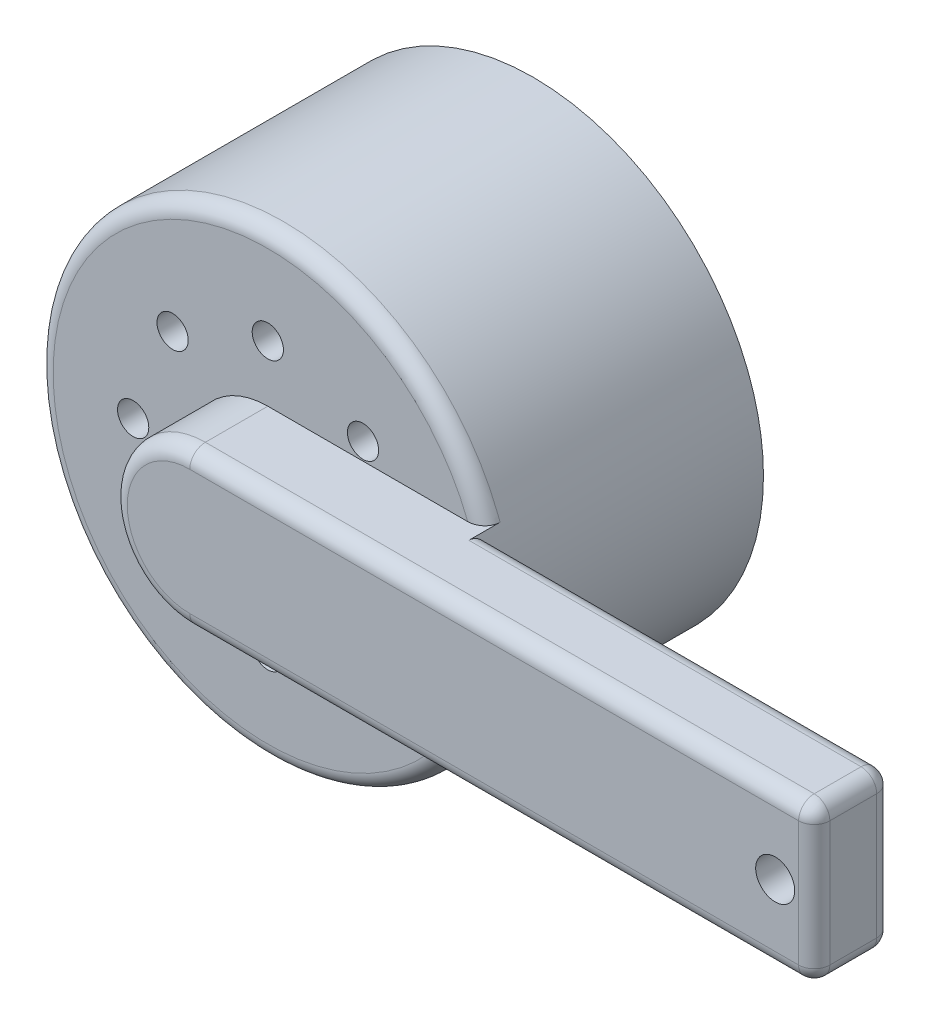
SolidWorks part; units mm, degrees
ref_plane "前视基准面" through (0, 0, 0) normal (0, 0, 1) x (1, 0, 0)
ref_plane "上视基准面" through (0, 0, 0) normal (0, 1, 0) x (1, 0, 0)
ref_plane "右视基准面" through (0, 0, 0) normal (1, 0, 0) x (0, 0, -1)
other "Configuration Table"
sketch "草图1" plane through (0, 0, 0) normal (0, 0, 1) x (1, 0, 0)
  circle A0 centre (0, 0) radius 29.5
extrude "凸台-拉伸2" add sketch "草图1" along normal mid plane 34
sketch "草图5" plane through (0, 0, 0) normal (0, 0, 1) x (1, 0, 0)
  circle A0 centre (0, 0) radius 17.25 construction
  circle A1 centre (-17.25, 0) radius 2
  circle A2 centre (-12.1976, 12.1976) radius 2
  circle A3 centre (0, 17.25) radius 2
  circle A4 centre (12.1976, 12.1976) radius 2
  circle A5 centre (17.25, 0) radius 2
  circle A6 centre (12.1976, -12.1976) radius 2
  circle A7 centre (0, -17.25) radius 2
  circle A8 centre (-12.1976, -12.1976) radius 2
  point P22 (0, 0)
  dimension "D1" = 34.5
  dimension "D2" = 4
  dimension "D3" = 34.5
  dimension "D4" = 8
extrude "切除-拉伸2" cut sketch "草图5" against normal mid plane 271.75
sketch "草图7" plane through (0, 0, 0) normal (0, 0, 1) x (1, 0, 0)
  circle A0 centre (0, 0) radius 10
  dimension "D1" = 20
extrude "凸台-拉伸5" add sketch "草图7" along normal blind 27
sketch "草图9" plane through (0, 0, 0) normal (1, 0, 0) x (0, 0, -1)
  line L0 (-27, 10) -> (-27, -10)
  line L1 (-27, -10) -> (-17, -10)
  line L2 (-27, -10) -> (-17, -10) construction
  line L3 (-17, -10) -> (-17, 10)
  line L4 (-17, 10) -> (-27, 10)
extrude "凸台-拉伸6" add sketch "草图9" along normal blind 80
sketch "草图10" plane through (0, 0, 0) normal (0, 0, 1) x (1, 0, 0)
  line L0 (80, 10) -> (80, -10) construction
  circle A0 centre (75, 0) radius 2.5
  dimension "D1" = 5
  dimension "D2" = 5
extrude "切除-拉伸3" cut sketch "草图10" against normal mid plane 80
fillet "圆角1" radius 2 3 edges at (53.8767, -10, 17) (53.8767, 10, 17) (80, 0, 17)
fillet "圆角2" radius 2 3 edges at (40, -10, 27) (-10, 0, 27) (40, 10, 27)
fillet "圆角3" radius 2 7 edges at (80, 10, 22) (79.4142, 9.4142, 17.5858) (79.4142, -9.4142, 17.5858) (80, -10, 22) (80, 0, 27) (80, 9.4142, 26.4142) (80, -9.4142, 26.4142)
fillet "圆角4" radius 2 1 edges at (-29.5, 0, 17)
